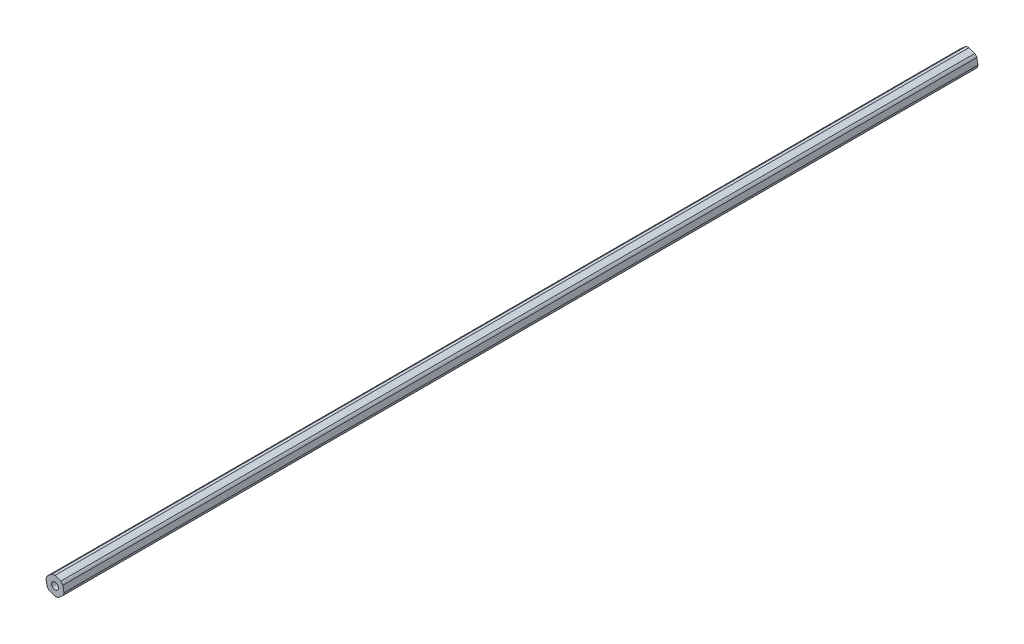
SolidWorks part; units mm, degrees
material "7075-T6 (SN)"
ref_plane "Front Plane" through (0, 0, 0) normal (0, 0, 1) x (1, 0, 0)
ref_plane "Top Plane" through (0, 0, 0) normal (0, 1, 0) x (1, 0, 0)
ref_plane "Right Plane" through (0, 0, 0) normal (1, 0, 0) x (0, 0, -1)
sketch "Sketch1" plane through (0, 0, 0) normal (0, 0, 1) x (1, 0, 0)
  line L1 (-6.6545, 1.1312) -> (-5.8457, -3.375)
  line L2 (-4.3069, -5.1974) -> (0, -6.75)
  line L3 (2.3476, -6.3286) -> (5.8457, -3.375)
  line L4 (6.6545, -1.1312) -> (5.8457, 3.375)
  line L5 (4.3069, 5.1974) -> (0, 6.75)
  line L6 (-2.3476, 6.3286) -> (-5.8457, 3.375)
  circle A0 centre (0, 0) radius 6.35 construction
  arc A1 (-5.8457, 3.375) -> (-6.6545, 1.1312) centre (0, 0) ccw
  arc A2 (-5.8457, -3.375) -> (-4.3069, -5.1974) centre (0, 0) ccw
  arc A3 (0, -6.75) -> (2.3476, -6.3286) centre (0, 0) ccw
  arc A4 (5.8457, -3.375) -> (6.6545, -1.1312) centre (0, 0) ccw
  arc A5 (5.8457, 3.375) -> (4.3069, 5.1974) centre (0, 0) ccw
  arc A6 (0, 6.75) -> (-2.3476, 6.3286) centre (0, 0) ccw
  dimension "D1" = 12.7
  dimension "D2" = 13.5
extrude "Boss-Extrude1" add sketch "Sketch1" along normal blind 678.3197
sketch "Sketch2" plane through (0, 0, 678.3197) normal (0, 0, 1) x (1, 0, 0)
  circle A0 centre (0, 0) radius 2.0193
  dimension "D1" = 4.0386
extrude "Cut-Extrude1" cut sketch "Sketch2" against normal through all
hole_wizard "1/4-20 Tapped Hole1" positions "Sketch5" profile "Sketch6" tap size "1/4-20" standard "ANSI Inch"
sketch "Sketch5" plane through (0, 0, 678.3197) normal (0, 0, 1) x (1, 0, 0)
  point P0 (0, 0)
sketch "Sketch6" plane through (0, 0, 678.3197) normal (1, 0, 0) x (0, -1, 0)
  line L0 (0, 0) -> (0, 20.5838)
  line L1 (0, 20.5838) -> (2.5527, 19.05)
  line L2 (2.5527, 19.05) -> (2.5527, 0)
  line L5 (2.5527, 0) -> (0, 0)
  line L10 (0, 20.5838) -> (-2.5527, 19.05) construction
  line L11 (0, -6.35) -> (0, 107.95) construction
  dimension "Tap Drill Dia." = 5.1054
  dimension "Tap Drill Depth" = 19.05
  dimension "Drill Angle" = 118
cosmetic thread "Hole Thread1" parameters "D1"=12.7, "D2"=6.35
hole_wizard "1/4-20 Tapped Hole2" positions "Sketch7" profile "Sketch8" tap size "1/4-20" standard "ANSI Inch"
sketch "Sketch7" plane through (0, 0, 0) normal (0, 0, -1) x (-1, 0, 0)
  point P0 (0, 0)
sketch "Sketch8" plane through (0, 0, 0) normal (1, 0, 0) x (0, 1, 0)
  line L0 (0, 0) -> (0, 20.5838)
  line L1 (0, 20.5838) -> (2.5527, 19.05)
  line L2 (2.5527, 19.05) -> (2.5527, 0)
  line L5 (2.5527, 0) -> (0, 0)
  line L10 (0, 20.5838) -> (-2.5527, 19.05) construction
  line L11 (0, -6.35) -> (0, 107.95) construction
  dimension "Tap Drill Dia." = 5.1054
  dimension "Tap Drill Depth" = 19.05
  dimension "Drill Angle" = 118
cosmetic thread "Hole Thread2" parameters "D1"=12.7, "D2"=6.35
